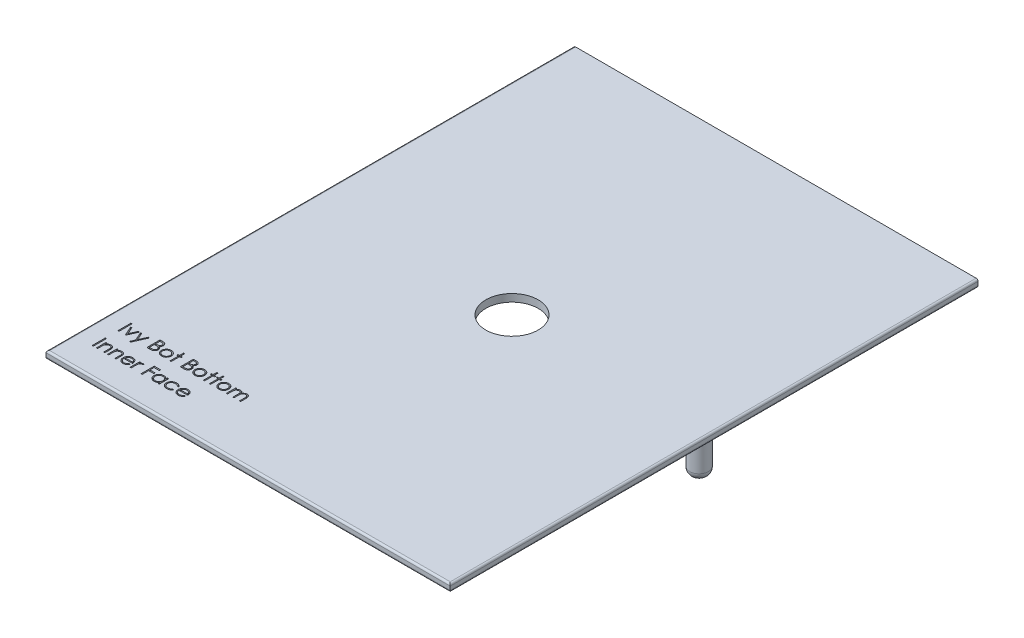
SolidWorks part; units mm, degrees
ref_plane "Front Plane" through (0, 0, 0) normal (0, 0, 1) x (1, 0, 0)
ref_plane "Top Plane" through (0, 0, 0) normal (0, 1, 0) x (1, 0, 0)
ref_plane "Right Plane" through (0, 0, 0) normal (1, 0, 0) x (0, 0, -1)
sketch "Sketch1" plane through (0, 0, 0) normal (0, 1, 0) x (1, 0, 0)
  line L1 (-54, 70.5) -> (54, 70.5)
  line L2 (-54, 70.5) -> (-54, -70.5)
  line L3 (-54, -70.5) -> (54, -70.5)
  line L4 (54, 70.5) -> (54, -70.5)
  point P4 (0, -70.5)
  point P6 (-54, 0)
  dimension "D1" = 108
  dimension "D2" = 141
extrude "Boss-Extrude1" add sketch "Sketch1" along normal blind 2 contours L1 L4 L3 L2
sketch "Sketch6" plane through (0, 2, 0) normal (0, 1, 0) x (1, 0, 0)
  circle A0 centre (0, 0) radius 7
  dimension "D1" = 14
extrude "Cut-Extrude1" cut sketch "Sketch6" against normal through all contours A0
fillet "Fillet1" radius 0.5 7 edges at (-54, 0, 0) (0, 0, -70.5) (0, 0, 70.5) (54, 0, 0) (54, 2, 0) (-54, 2, 0) (0, 2, 70.5)
sketch "Sketch9" plane through (0, 2, 0) normal (0, 1, 0) x (1, 0, 0)
  text T0 "Ivy Bot Bottom\r\nInner Face"
extrude "Cut-Extrude4" cut sketch "Sketch9" against normal blind 1
sketch "Sketch10" plane through (0, 0, 0) normal (0, -1, 0) x (1, 0, 0)
  line L0 (-12.9733, 25) -> (12.9733, 25) construction
  line L1 (-12.9733, -25) -> (12.9733, -25) construction
  text T0 "3               1"
  text T1 " 2               4"
  point P8 (0, 25)
  point P12 (0, -25)
  dimension "D1" = 25
  dimension "D2" = 25
extrude "Cut-Extrude5" cut sketch "Sketch10" against normal blind 1
sketch "Sketch11" plane through (0, 0, 0) normal (0, -1, 0) x (1, 0, 0)
  line L0 (0, 70) -> (0, -70) construction
  line L1 (53.5, 70) -> (-53.5, 70) construction
  line L2 (-53.5, -70) -> (53.5, -70) construction
  line L3 (-53.5, 0) -> (53.5, 0) construction
  line L4 (53.5, -70) -> (53.5, 70) construction
  line L5 (50, 0) -> (-50, 0) construction
  circle A0 centre (-50, 0) radius 2.5
  circle A1 centre (50, 0) radius 2.5
  point P13 (0, 0)
  point P17 (0, 0)
extrude "Boss-Extrude2" add sketch "Sketch11" along normal blind 10
fillet "Fillet4" radius 2 2 edges at (50, -10, 2.5) (-50, -10, -2.5)
